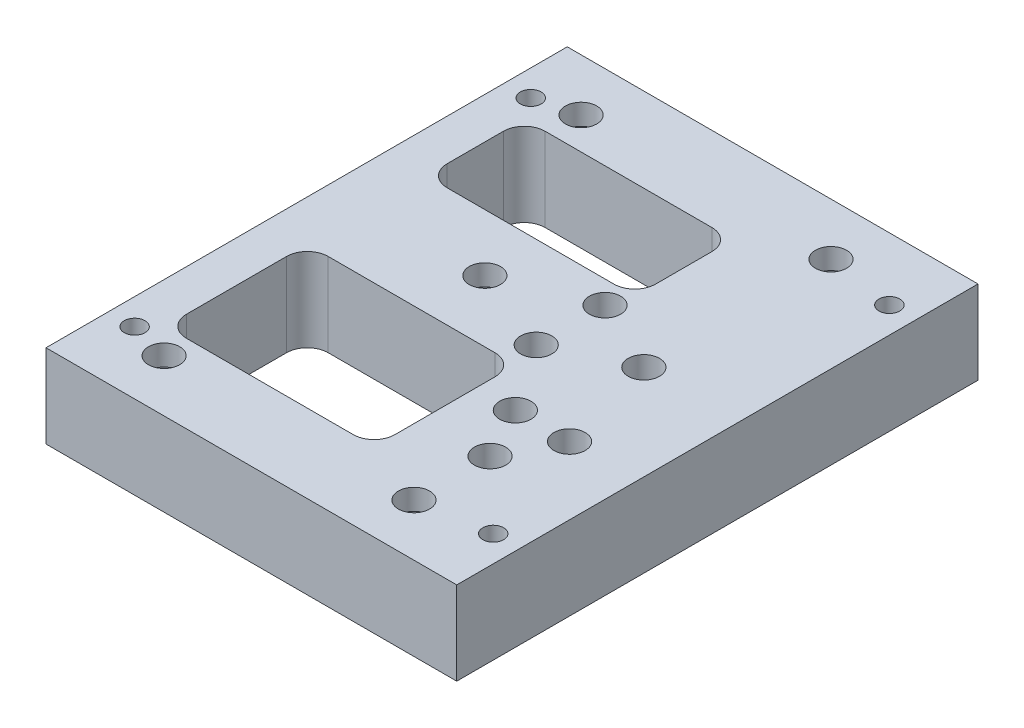
SolidWorks part; units mm, degrees
material "K110"
ref_plane "Front Plane" through (0, 0, 0) normal (0, 0, 1) x (1, 0, 0)
ref_plane "Top Plane" through (0, 0, 0) normal (0, 1, 0) x (1, 0, 0)
ref_plane "Right Plane" through (0, 0, 0) normal (1, 0, 0) x (0, 0, -1)
sketch "Sketch1" plane through (0, 0, 0) normal (0, 1, 0) x (1, 0, 0)
  line L1 (-98.5, -125) -> (98.5, -125)
  line L2 (-98.5, -125) -> (-98.5, 125)
  line L3 (-98.5, 125) -> (98.5, 125)
  line L4 (98.5, -125) -> (98.5, 125)
  line L5 (-98.5, -125) -> (98.5, 125) construction
  line L6 (-98.5, 125) -> (98.5, -125) construction
  point P0 (0, 0)
  dimension "D1" = 250
  dimension "D2" = 197
extrude "Boss-Extrude1" add sketch "Sketch1" against normal blind 40
sketch "Sketch2" plane through (0, 0, 0) normal (0, 1, 0) x (1, 0, 0)
  line L0 (-29.25, -63.53) -> (-29.25, -47.4) construction
  line L1 (-32.25, -44.4) -> (-36.25, -44.4) construction
  line L2 (-42.25, -38.4) -> (-42.25, -32.27) construction
  line L3 (-42.25, -32.27) -> (-61.37, -32.27) construction
  line L12 (-64.37, -35.27) -> (-64.37, -71.53) construction
  line L13 (-61.37, -74.53) -> (3.88, -74.53) construction
  line L14 (-17.25, -47.4) -> (-17.25, -63.53) construction
  line L15 (-10.25, -44.4) -> (-14.25, -44.4) construction
  line L16 (-4.25, -32.27) -> (-4.25, -38.4) construction
  line L17 (3.88, -32.27) -> (-4.25, -32.27) construction
  line L18 (6.88, -71.53) -> (6.88, -35.27) construction
  line L19 (-29.25, -63.53) -> (-29.25, -47.4)
  line L20 (-32.25, -44.4) -> (-36.25, -44.4)
  line L21 (-42.25, -38.4) -> (-42.25, -32.27)
  line L22 (-42.25, -32.27) -> (-61.37, -32.27)
  line L23 (-64.37, -35.27) -> (-64.37, -71.53)
  line L24 (-61.37, -74.53) -> (3.88, -74.53)
  line L25 (-17.25, -47.4) -> (-17.25, -63.53)
  line L26 (-10.25, -44.4) -> (-14.25, -44.4)
  line L27 (-4.25, -32.27) -> (-4.25, -38.4)
  line L28 (3.88, -32.27) -> (-4.25, -32.27)
  line L29 (6.88, -71.53) -> (6.88, -35.27)
  line L30 (-4.25, 47.73) -> (3.88, 47.73) construction
  line L31 (-4.25, 69.53) -> (-4.25, 47.73) construction
  line L32 (-42.25, 69.53) -> (-4.25, 69.53) construction
  line L33 (-42.25, 47.73) -> (-42.25, 69.53) construction
  line L34 (-61.37, 47.73) -> (-42.25, 47.73) construction
  line L35 (-64.37, 71.53) -> (-64.37, 50.73) construction
  line L36 (3.88, 74.53) -> (-61.37, 74.53) construction
  line L37 (6.88, 50.73) -> (6.88, 71.53) construction
  line L38 (-4.25, 47.73) -> (3.88, 47.73)
  line L39 (-4.25, 69.53) -> (-4.25, 47.73)
  line L40 (-42.25, 69.53) -> (-4.25, 69.53)
  line L41 (-42.25, 47.73) -> (-42.25, 69.53)
  line L42 (-61.37, 47.73) -> (-42.25, 47.73)
  line L43 (-64.37, 71.53) -> (-64.37, 50.73)
  line L44 (3.88, 74.53) -> (-61.37, 74.53)
  line L45 (6.88, 50.73) -> (6.88, 71.53)
  arc A0 (-29.25, -47.4) -> (-32.25, -44.4) centre (-32.25, -47.4) ccw construction
  arc A1 (-42.25, -38.4) -> (-36.25, -44.4) centre (-36.25, -38.4) ccw construction
  arc A2 (-61.37, -32.27) -> (-64.37, -35.27) centre (-61.37, -35.27) ccw construction
  arc A3 (-64.37, -71.53) -> (-61.37, -74.53) centre (-61.37, -71.53) ccw construction
  arc A4 (3.88, -74.53) -> (6.88, -71.53) centre (3.88, -71.53) ccw construction
  arc A5 (-29.25, -63.53) -> (-17.25, -63.53) centre (-23.25, -63.53) ccw construction
  arc A6 (-14.25, -44.4) -> (-17.25, -47.4) centre (-14.25, -47.4) ccw construction
  arc A7 (-10.25, -44.4) -> (-4.25, -38.4) centre (-10.25, -38.4) ccw construction
  arc A8 (6.88, -35.27) -> (3.88, -32.27) centre (3.88, -35.27) ccw construction
  arc A9 (-29.25, -47.4) -> (-32.25, -44.4) centre (-32.25, -47.4) ccw
  arc A10 (-42.25, -38.4) -> (-36.25, -44.4) centre (-36.25, -38.4) ccw
  arc A11 (-61.37, -32.27) -> (-64.37, -35.27) centre (-61.37, -35.27) ccw
  arc A12 (-64.37, -71.53) -> (-61.37, -74.53) centre (-61.37, -71.53) ccw
  arc A13 (3.88, -74.53) -> (6.88, -71.53) centre (3.88, -71.53) ccw
  arc A14 (-29.25, -63.53) -> (-17.25, -63.53) centre (-23.25, -63.53) ccw
  arc A15 (-14.25, -44.4) -> (-17.25, -47.4) centre (-14.25, -47.4) ccw
  arc A16 (-10.25, -44.4) -> (-4.25, -38.4) centre (-10.25, -38.4) ccw
  arc A17 (6.88, -35.27) -> (3.88, -32.27) centre (3.88, -35.27) ccw
  circle A18 centre (53, -63.53) radius 2.5 construction
  circle A19 centre (66, -38.4) radius 2.5 construction
  circle A20 centre (40, -38.4) radius 2.5 construction
  circle A21 centre (17.88, -6.27) radius 2.5 construction
  circle A22 centre (17.88, 26.73) radius 2.5 construction
  arc A23 (3.88, 47.73) -> (6.88, 50.73) centre (3.88, 50.73) ccw construction
  arc A24 (-64.37, 50.73) -> (-61.37, 47.73) centre (-61.37, 50.73) ccw construction
  arc A25 (-61.37, 74.53) -> (-64.37, 71.53) centre (-61.37, 71.53) ccw construction
  arc A26 (6.88, 71.53) -> (3.88, 74.53) centre (3.88, 71.53) ccw construction
  circle A27 centre (53, -63.53) radius 2.5
  circle A28 centre (66, -38.4) radius 2.5
  circle A29 centre (40, -38.4) radius 2.5
  circle A30 centre (17.88, -6.27) radius 2.5
  circle A31 centre (17.88, 26.73) radius 2.5
  arc A32 (3.88, 47.73) -> (6.88, 50.73) centre (3.88, 50.73) ccw
  arc A33 (-64.37, 50.73) -> (-61.37, 47.73) centre (-61.37, 50.73) ccw
  arc A34 (-61.37, 74.53) -> (-64.37, 71.53) centre (-61.37, 71.53) ccw
  arc A35 (6.88, 71.53) -> (3.88, 74.53) centre (3.88, 71.53) ccw
sketch "Sketch3" plane through (0, 0, 0) normal (0, 1, 0) x (1, 0, 0)
  line L1 (-68.745, 84.63) -> (11.255, 84.63)
  line L2 (-78.745, 74.63) -> (-78.745, 47.63)
  line L3 (-68.745, 37.63) -> (11.255, 37.63)
  line L4 (21.255, 74.63) -> (21.255, 47.63)
  line L8 (-64.37, -53.4) -> (6.88, -53.4) construction
  line L9 (-68.745, -19.4) -> (11.255, -19.4)
  line L10 (-78.745, -29.4) -> (-78.745, -77.4)
  line L11 (-68.745, -87.4) -> (11.255, -87.4)
  line L12 (21.255, -29.4) -> (21.255, -77.4)
  line L13 (-64.37, -35.27) -> (-64.37, -71.53) construction
  line L14 (6.88, -71.53) -> (6.88, -35.27) construction
  line L15 (-28.745, -74.53) -> (-28.745, -19.4) construction
  line L16 (-61.37, -74.53) -> (3.88, -74.53) construction
  line L17 (-28.745, 84.63) -> (-28.745, 47.73) construction
  line L18 (-64.37, 61.13) -> (6.88, 61.13) construction
  line L19 (-64.37, 71.53) -> (-64.37, 50.73) construction
  line L20 (6.88, 50.73) -> (6.88, 71.53) construction
  arc A0 (-78.745, 47.63) -> (-68.745, 37.63) centre (-68.745, 47.63) ccw
  arc A1 (11.255, 37.63) -> (21.255, 47.63) centre (11.255, 47.63) ccw
  arc A2 (21.255, 74.63) -> (11.255, 84.63) centre (11.255, 74.63) ccw
  arc A3 (-68.745, 84.63) -> (-78.745, 74.63) centre (-68.745, 74.63) ccw
  circle A4 centre (17.88, 26.73) radius 7.5
  circle A5 centre (17.88, -6.27) radius 7.5
  circle A6 centre (53, -63.53) radius 7.5
  circle A7 centre (66, -38.4) radius 7.5
  circle A8 centre (40, -38.4) radius 7.5
  arc A9 (-78.745, -77.4) -> (-68.745, -87.4) centre (-68.745, -77.4) ccw
  arc A10 (11.255, -87.4) -> (21.255, -77.4) centre (11.255, -77.4) ccw
  arc A11 (21.255, -29.4) -> (11.255, -19.4) centre (11.255, -29.4) ccw
  arc A12 (-68.745, -19.4) -> (-78.745, -29.4) centre (-68.745, -29.4) ccw
  dimension "D5" = 10
  dimension "D6" = 15
  dimension "D11" = 10
  dimension "D2" = 100
  dimension "D3" = 47
  dimension "D7" = 68
  dimension "D8" = 100
extrude "Cut-Extrude2" cut sketch "Sketch3" against normal up to next
sketch "Sketch4" plane through (0, -40, 0) normal (0, -1, 0) x (1, 0, 0)
  circle A0 centre (17.88, -26.73) radius 9
  circle A1 centre (17.88, 6.27) radius 9
  circle A2 centre (40, 38.4) radius 9
  circle A3 centre (66, 38.4) radius 9
  circle A4 centre (53, 63.53) radius 9
  dimension "D1" = 18
extrude "Cut-Extrude3" cut sketch "Sketch4" against normal blind 5
extrude "Cut-Extrude9" cut sketch "Sketch11" against normal through all
sketch "Sketch11" plane through (88.13, 0, 0) normal (0, 1, 0) x (1, 0, 0)
  circle A0 centre (-35.13, 10.23) radius 7.5
  circle A1 centre (-111.38, 10.23) radius 7.5
extrude "Cut-Extrude10" cut sketch "Sketch12" against normal blind 5
sketch "Sketch12" plane through (88.13, -40, 0) normal (0, -1, 0) x (1, 0, 0)
  circle A0 centre (-35.13, -10.23) radius 10
extrude "Cut-Extrude11" cut sketch "Sketch13" against normal blind 30
sketch "Sketch13" plane through (88.13, -40, 0) normal (0, -1, 0) x (1, 0, 0)
  circle A0 centre (-111.38, -10.23) radius 10
hole_wizard "M10 Tapped Hole1" positions "Sketch27" profile "Sketch15" tap size "M10" standard "ISO"
sketch "Sketch27" plane through (0, -40, 0) normal (0, -1, 0) x (-1, 0, 0)
  line L0 (-98.5, -125) -> (-98.5, 125) construction
  line L1 (-98.5, 125) -> (98.5, 125) construction
  line L2 (98.5, 125) -> (98.5, -125) construction
  line L3 (98.5, -125) -> (-98.5, -125) construction
  point P0 (-86, 112.5)
  point P2 (86, 112.5)
  point P4 (86, -112.5)
  point P6 (-86, -112.5)
  dimension "D1" = 12.5
  dimension "D2" = 12.5
  dimension "D3" = 12.5
  dimension "D4" = 12.5
sketch "Sketch15" plane through (86, -40, -112.5) normal (1, 0, 0) x (0, 0, -1)
  line L0 (0, 0) -> (0, 30.0537)
  line L1 (0, 30.0537) -> (4.25, 27.5)
  line L2 (4.25, 27.5) -> (4.25, 0.775)
  line L3 (4.25, 0.775) -> (5.025, 0)
  line L5 (5.025, 0) -> (0, 0)
  line L6 (-4.25, 0.775) -> (-5.025, 0) construction
  line L10 (0, 30.0537) -> (-4.25, 27.5) construction
  line L11 (0, -6.35) -> (0, 107.95) construction
  dimension "Tap Drill Dia." = 8.5
  dimension "Tap Drill Depth" = 27.5
  dimension "Near C'Sink Dia." = 10.05
  dimension "Near C'Sink Angle" = 90
  dimension "Drill Angle" = 118
cosmetic thread "Hole Thread1" parameters "D1"=20, "D2"=10
cosmetic thread "Hole Thread2" parameters "D1"=20, "D2"=10
cosmetic thread "Hole Thread3" parameters "D1"=20, "D2"=10
cosmetic thread "Hole Thread4" parameters "D1"=20, "D2"=10
hole_wizard "Ø10.0mm Dowel Hole2" positions "Sketch26" profile "Sketch25" hole size "Ø10.0" standard "ISO" end condition through all
sketch "Sketch26" plane through (0, -40, 0) normal (0, -1, 0) x (-1, 0, 0)
  line L0 (-98.5, -125) -> (-98.5, 125) construction
  line L1 (98.5, 125) -> (98.5, -125) construction
  circle A0 centre (-86, 112.5) radius 4.25 construction
  circle A1 centre (-86, -112.5) radius 4.25 construction
  point P0 (-86, 95)
  point P2 (86, 95)
  point P4 (86, -95)
  point P6 (-86, -95)
  point P15 (0, 0)
  point P16 (0, 0)
  point P17 (0, 0)
  point P18 (0, 0)
  dimension "D4" = 17.5
  dimension "D1" = 12.5
  dimension "D2" = 17.5
  dimension "D3" = 12.5
sketch "Sketch25" plane through (86, -40, -95) normal (1, 0, 0) x (0, 0, -1)
  line L0 (0, 0) -> (0, 40)
  line L1 (0, 40) -> (5, 40)
  line L2 (5, 40) -> (5, 0)
  line L5 (5, 0) -> (0, 0)
  line L11 (0, -6.35) -> (0, 107.95) construction
  dimension "Thru Hole Dia." = 10
  dimension "Thru Hole Depth" = 40
sketch "Sketch28" plane through (0, 0, 0) normal (0, 1, 0) x (1, 0, 0)
  line L0 (-374.37, -95) -> (88.13, -95) construction
  line L1 (53, -63.53) -> (53, -100) construction
  line L2 (-64.37, -71.53) -> (-69.37, -71.53) construction
  line L3 (-66.87, -71.53) -> (-66.87, -100) construction
  circle A0 centre (53, -100) radius 7.5
  circle A4 centre (-66.87, -100) radius 7.5
  dimension "D1" = 15
  dimension "D2" = 5
extrude "Cut-Extrude12" cut sketch "Sketch28" against normal up to next
mirror "Mirror1" about plane through (0, 0, 0) normal (0, 0, 1) of "Cut-Extrude12"
sketch "Sketch29" plane through (0, -40, 0) normal (0, -1, 0) x (1, 0, 0)
  circle A0 centre (-66.87, 100) radius 9
  circle A1 centre (53, 100) radius 9
  circle A2 centre (53, -100) radius 9
  circle A3 centre (-66.87, -100) radius 9
  dimension "D1" = 18
extrude "Cut-Extrude13" cut sketch "Sketch29" against normal blind 30
